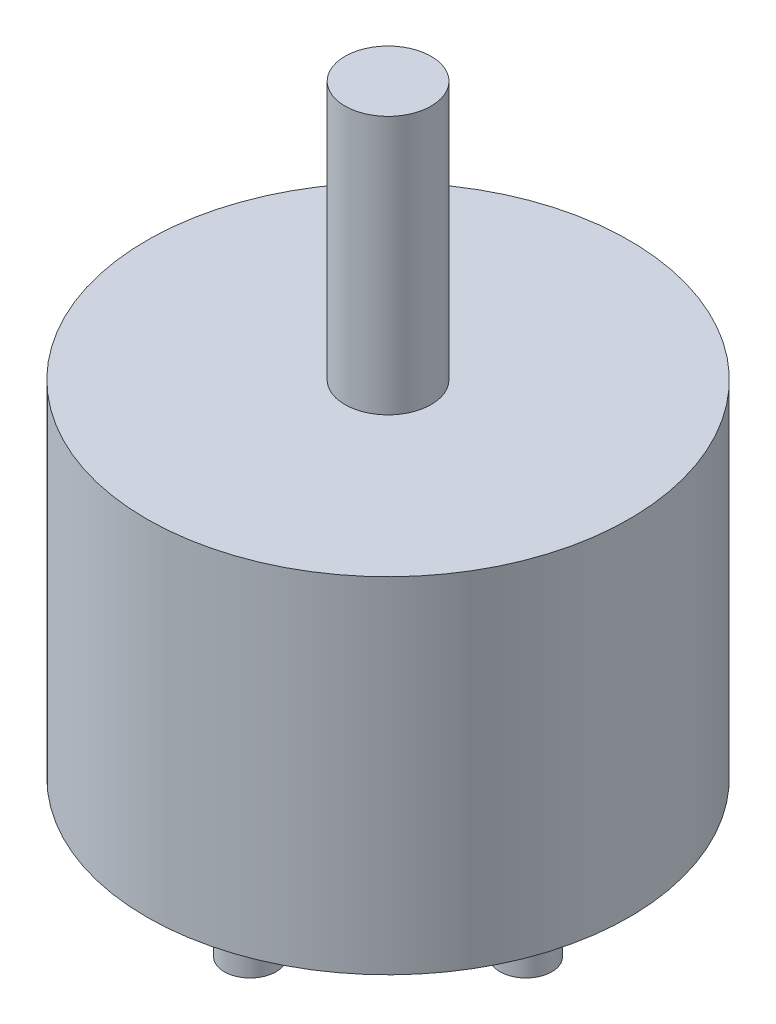
SolidWorks part; units mm, degrees
ref_plane "Plan de face" through (0, 0, 0) normal (0, 0, 1) x (1, 0, 0)
ref_plane "Plan de dessus" through (0, 0, 0) normal (0, 1, 0) x (1, 0, 0)
ref_plane "Plan de droite" through (0, 0, 0) normal (1, 0, 0) x (0, 0, -1)
sketch "Esquisse1" plane through (0, 0, 0) normal (0, 1, 0) x (1, 0, 0)
  circle A0 centre (0, 0) radius 14
extrude "Boss.-Extru.1" add sketch "Esquisse1" along normal blind 20
sketch "Esquisse2" plane through (0, 20, 0) normal (0, 1, 0) x (1, 0, 0)
  circle A0 centre (0, 0) radius 2.5
extrude "Boss.-Extru.2" add sketch "Esquisse2" along normal blind 15
sketch "Esquisse3" plane through (0, 0, 0) normal (0, -1, 0) x (-1, 0, 0)
  circle A1 centre (-8, 0) radius 1.5
  circle A2 centre (0, 8) radius 1.5
  circle A3 centre (8, 0) radius 1.4381
  circle A4 centre (0, -8) radius 1.5
  dimension "D1" = 8
  dimension "D2" = 8
  dimension "D4" = 8
  dimension "D3" = 8
extrude "Boss.-Extru.3" add sketch "Esquisse3" along normal blind 5
